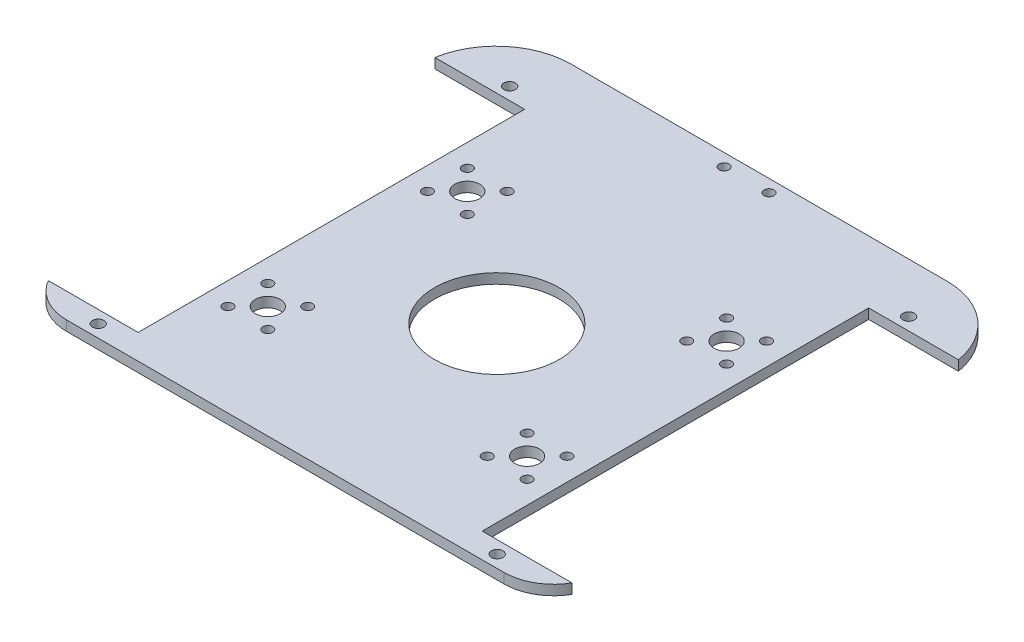
SolidWorks part; units mm, degrees
ref_plane "Front Plane" through (0, 0, 0) normal (0, 0, 1) x (1, 0, 0)
ref_plane "Top Plane" through (0, 0, 0) normal (0, 1, 0) x (1, 0, 0)
ref_plane "Right Plane" through (0, 0, 0) normal (1, 0, 0) x (0, 0, -1)
sketch "Sketch1" plane through (0, 0, 0) normal (0, 1, 0) x (1, 0, 0)
  line L0 (-153.1481, 80) -> (-117.1481, 80)
  line L2 (56.8519, 105) -> (56.8519, 80)
  line L3 (56.8519, -85) -> (-153.1481, -85)
  line L4 (-153.1481, 105) -> (-153.1481, 80)
  line L5 (-153.1481, 105) -> (56.8519, 105)
  line L6 (-117.1481, 2.5) -> (-153.1481, 2.5) construction
  line L7 (-117.1481, 80) -> (-117.1481, -75)
  line L8 (-117.1481, -75) -> (-153.1481, -75)
  line L9 (-48.1481, 105) -> (-48.1481, -85) construction
  line L10 (20.8519, -75) -> (56.8519, -75)
  line L11 (20.8519, 80) -> (20.8519, -75)
  line L12 (56.8519, 80) -> (20.8519, 80)
  line L13 (-153.1481, -75) -> (-153.1481, -85)
  line L14 (56.8519, -75) -> (56.8519, -85)
  line L15 (-48.1481, -40) -> (-117.1481, -40) construction
  line L16 (-48.1481, 0) -> (-117.1481, 0) construction
  circle A1 centre (-48.296, 0.0001) radius 25
  circle A2 centre (-57.1481, 100) radius 2
  circle A3 centre (-39.1481, 100) radius 2
  circle A4 centre (-128.1481, -80) radius 2.32
  circle A5 centre (-128.1481, 85) radius 2.32
  circle A6 centre (31.8519, 85) radius 2.32
  circle A7 centre (31.8519, -80) radius 2.32
  circle A8 centre (-108.1481, -48) radius 2
  circle A9 centre (-92.1481, -48) radius 2
  circle A10 centre (-92.1481, -32) radius 2
  circle A11 centre (-108.1481, -32) radius 2
  circle A12 centre (-100.1481, -40) radius 5
  circle A13 centre (-92.1481, 48) radius 2
  circle A14 centre (-108.1481, 48) radius 2
  circle A15 centre (-92.1481, 32) radius 2
  circle A16 centre (-100.1481, 40) radius 5
  circle A17 centre (-108.1481, 32) radius 2
  circle A18 centre (-4.1481, -32) radius 2
  circle A19 centre (-4.1481, -48) radius 2
  circle A20 centre (3.8519, -40) radius 5
  circle A21 centre (11.8519, -48) radius 2
  circle A22 centre (11.8519, -32) radius 2
  circle A23 centre (-4.1481, 32) radius 2
  circle A24 centre (-4.1481, 48) radius 2
  circle A25 centre (11.8519, 32) radius 2
  circle A26 centre (11.8519, 48) radius 2
  circle A27 centre (3.8519, 40) radius 5
  point P0 (0, 0)
  point P20 (-153.1481, -80)
  dimension "D9" = 5
  dimension "D7" = 105
  dimension "D10" = 25
  dimension "D2" = 9
  dimension "D12" = 27
  dimension "D14" = 16
  dimension "D17" = 8
  dimension "D1" = 210
  dimension "D3" = 36
  dimension "D4" = 155
  dimension "D5" = 10
  dimension "D6" = 25
  dimension "D8" = 25
  dimension "D11" = 5
  dimension "D13" = 9
  dimension "D15" = 27
  dimension "D16" = 8
  dimension "D18" = 32
extrude "Boss-Extrude1" add sketch "Sketch1" along normal blind 4
fillet "Fillet1" radius 30 2 edges at (56.8519, 2, -105) (-153.1481, 2, -105)
fillet "Fillet2" radius 20 2 edges at (56.8519, 2, 85) (-153.1481, 2, 85)
